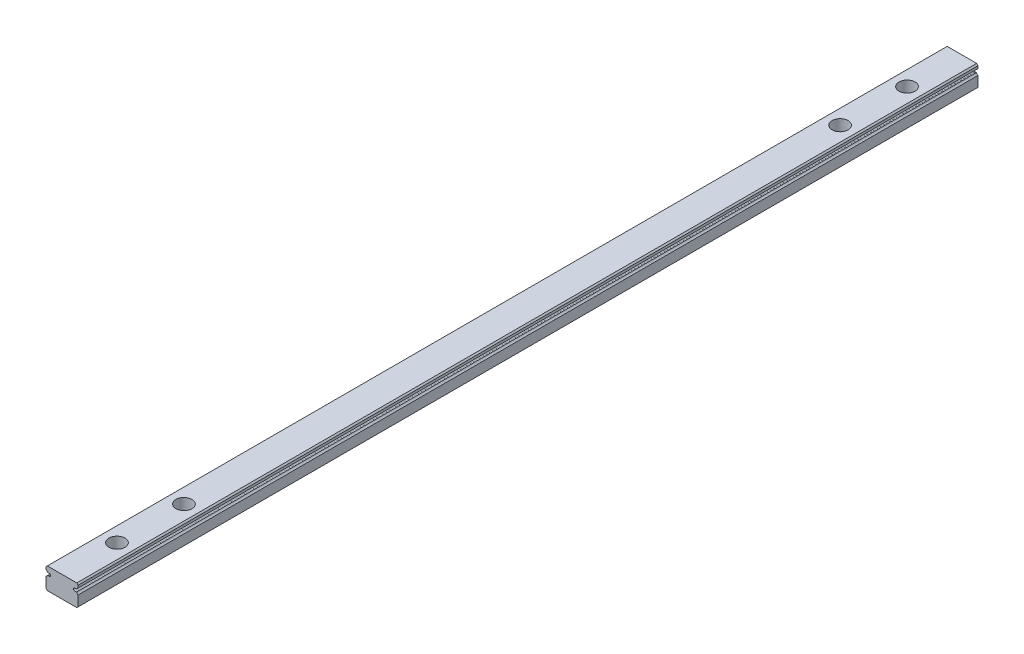
SolidWorks part; units mm, degrees
material "Chrome Stainless Steel"
ref_plane "Front Plane" through (0, 0, 0) normal (0, 0, 1) x (1, 0, 0)
ref_plane "Top Plane" through (0, 0, 0) normal (0, 1, 0) x (1, 0, 0)
ref_plane "Right Plane" through (0, 0, 0) normal (1, 0, 0) x (0, 0, -1)
sketch "Sketch1" plane through (0, 0, 0) normal (0, 0, 1) x (1, 0, 0)
  line L0 (0, 4) -> (0, -4) construction
  line L1 (5.5, -4) -> (-5.5, -4)
  line L2 (-5.5, -4) -> (-6, -3.5)
  line L3 (-6, -3.5) -> (-6, 0.3689)
  line L4 (5.5, 4) -> (-5.5, 4)
  line L5 (-5.5, 4) -> (-6, 3.5)
  line L6 (-6, 2.5511) -> (-6, 3.5)
  line L7 (-5.3839, 0.985) -> (-4.9211, 0.985)
  line L8 (-5.3839, 1.935) -> (-4.9211, 1.935)
  line L9 (5.3839, 0.985) -> (4.9211, 0.985)
  line L10 (5.5, 4) -> (6, 3.5)
  line L11 (6, 2.5511) -> (6, 3.5)
  line L12 (5.3839, 1.935) -> (4.9211, 1.935)
  line L13 (6, -3.5) -> (6, 0.3689)
  line L14 (5.5, -4) -> (6, -3.5)
  circle A0 centre (-6.475, 1.46) radius 1.19 construction
  circle A1 centre (-4.765, 1.46) radius 0.5 construction
  arc A2 (-6, 0.3689) -> (-5.3839, 0.985) centre (-6.475, 1.46) ccw
  arc A3 (-5.3839, 1.935) -> (-6, 2.5511) centre (-6.475, 1.46) ccw
  arc A4 (-4.9211, 0.985) -> (-4.9211, 1.935) centre (-4.765, 1.46) ccw
  arc A5 (5.3839, 1.935) -> (6, 2.5511) centre (6.475, 1.46) cw
  arc A6 (4.9211, 0.985) -> (4.9211, 1.935) centre (4.765, 1.46) cw
  arc A7 (6, 0.3689) -> (5.3839, 0.985) centre (6.475, 1.46) cw
  point P4 (0, 0)
  point P32 (0, 0)
  dimension "D5" = 5.46
  dimension "D6" = 6.475
  dimension "D7" = 2.38
  dimension "D11" = 1
  dimension "D12" = 5.46
  dimension "D13" = 4.765
  dimension "D1" = 8
  dimension "D2" = 0.5
  dimension "D3" = 0.5
  dimension "D4" = 6
  dimension "D8" = 0.5
  dimension "D9" = 0.5
  dimension "D10" = 6
  dimension "D14" = 0.475
  dimension "D15" = 0.475
extrude "Boss-Extrude1" add sketch "Sketch1" along normal blind 420 contours L13 A7 L9 A6 L12 A5 L11 L10 L4 L5 L6 A3 L8 A4 L7 A2 L3 L2 L1 L14 region at (0, -0.0654, 0)
sketch "Sketch2" plane through (0, 4, 0) normal (0, 1, 0) x (1, 0, 0)
  line L0 (5.5, 0) -> (-5.5, 0) construction
  circle A0 centre (0, -12.5) radius 3
  dimension "D1" = 12.5
extrude "Cut-Extrude1" cut sketch "Sketch2" against normal blind 4.5
sketch "Sketch3" plane through (0, -0.5, 0) normal (0, 1, 0) x (1, 0, 0)
  circle A0 centre (0, -12.5) radius 1.75
extrude "Cut-Extrude2" cut sketch "Sketch3" against normal through all
pattern_linear "LPattern1" count 4 spacing 25 along (0, 0, 1) of "Cut-Extrude1", "Cut-Extrude2"
sketch "Sketch4" plane through (0, 4, 0) normal (0, 1, 0) x (1, 0, 0)
  line L0 (-6, -420) -> (-6, 0) construction
  point P0 (-6, -210)
ref_plane "Plane1" through (0, 0, 210) normal (0, 0, 1) x (1, 0, 0)
mirror "Mirror1" about plane through (0, 0, 210) normal (0, 0, 1) of "LPattern1", "Cut-Extrude2", "Cut-Extrude1"
sketch "Sketch5" plane through (0, 4, 0) normal (0, 1, 0) x (1, 0, 0)
  line L0 (-6, -378) -> (6, -378)
  line L1 (6, 0) -> (-6, 0)
  line L2 (6, 0) -> (6, -420)
  line L3 (6, -420) -> (-6, -420)
  line L4 (-6, 0) -> (-6, -420)
  circle M6 centre (0, -382.5) radius 3
  circle M9 centre (0, -407.5) radius 3
  line M15 (-5.5, 0) -> (-5.5, -420)
  line M16 (-5.5, -420) -> (5.5, -420)
  line M17 (5.5, -420) -> (5.5, 0)
  dimension "D1" = 42
extrude "Cut-Extrude3" cut sketch "Sketch5" against normal through all contours L0 M15 M16 M17 M9 M6 | M6 | M9 | L3 L2 L0 M17 | L0 L4 L3 M15 region at (-5.75, 4, 399) region at (0, 4, 399.5579) region at (5.75, 4, 399) region at (0, 4, 382.5) region at (0, 4, 407.5)
mirror "Mirror2" about plane through (0, 0, 210) normal (0, 0, 1) of "Cut-Extrude3"
